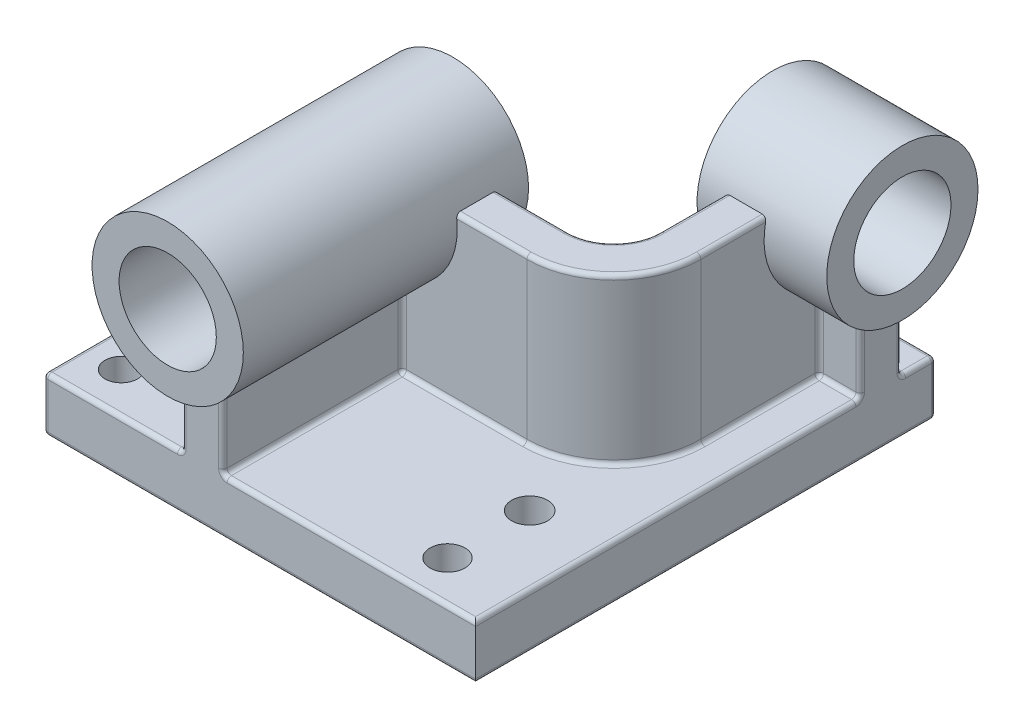
SolidWorks part; units mm, degrees
material "AISI 1020"
ref_plane "Front Plane" through (0, 0, 0) normal (0, 0, 1) x (1, 0, 0)
ref_plane "Top Plane" through (0, 0, 0) normal (0, 1, 0) x (1, 0, 0)
ref_plane "Right Plane" through (0, 0, 0) normal (1, 0, 0) x (0, 0, -1)
sketch "Sketch1" plane through (0, 0, 0) normal (0, 1, 0) x (1, 0, 0)
  line L0 (-200, 0) -> (0, 0)
  line L5 (0, 0) -> (0, 213)
  line L7 (-200, 0) -> (-200, 102)
  line L8 (-200, 102) -> (-59.2598, 102)
  line L9 (-38, 123.2598) -> (-38, 213)
  line L11 (-38, 213) -> (0, 213)
  arc A0 (-59.2598, 102) -> (-38, 123.2598) centre (-59.2598, 123.2598) ccw
  dimension "D1" = 200
  dimension "D2" = 213
  dimension "D3" = 38
  dimension "D4" = 102
extrude "Boss-Extrude1" add sketch "Sketch1" along normal blind 25
sketch "Sketch2" plane through (0, 25, 0) normal (0, 1, 0) x (1, 0, 0)
  line L0 (-200, 0) -> (0, 0) construction
  line L1 (-117, 0) -> (-136, 0)
  line L2 (-117, 0) -> (-117, 102)
  line L3 (-117, 102) -> (-136, 102)
  line L4 (-136, 0) -> (-136, 102)
  line L5 (-59.2598, 102) -> (-200, 102) construction
  line L6 (-200, 102) -> (-200, 0) construction
  dimension "D1" = 83
  dimension "D2" = 19
extrude "Boss-Extrude2" add sketch "Sketch2" along normal blind 76
sketch "Sketch3" plane through (0, 25, 0) normal (0, 1, 0) x (1, 0, 0)
  line L0 (-117, 102) -> (-59.2598, 102)
  line L1 (-38, 123.2598) -> (-38, 213)
  arc A0 (-59.2598, 102) -> (-38, 123.2598) centre (-59.2598, 123.2598) ccw
  arc A1 (-59.2598, 102) -> (-38, 123.2598) centre (-59.2598, 123.2598) ccw construction
extrude "Extrude-Thin1" add sketch "Sketch3" along normal blind 76 thin
sketch "Sketch4" plane through (0, 25, 0) normal (0, 1, 0) x (1, 0, 0)
  line L0 (0, 0) -> (0, 213) construction
  line L1 (0, 197) -> (-19, 197)
  line L2 (0, 197) -> (0, 178)
  line L3 (0, 178) -> (-19, 178)
  line L4 (-19, 197) -> (-19, 178)
  line L5 (-19, 123.2598) -> (-19, 213) construction
  line L6 (0, 213) -> (-19, 213) construction
  dimension "D1" = 35
  dimension "D2" = 19
extrude "Boss-Extrude3" add sketch "Sketch4" along normal blind 76
sketch "Sketch6" plane through (0, 0, 0) normal (0, 0, 1) x (1, 0, 0)
  line L0 (-126.5, 101) -> (-126.5, 73.6878) construction
  line L1 (-136, 101) -> (-117, 101) construction
  circle A0 centre (-126.5, 94.9895) radius 35
  circle A1 centre (-126.5, 94.9895) radius 22.5
  dimension "D1" = 70
  dimension "D2" = 45
extrude "Boss-Extrude4" add sketch "Sketch6" against normal blind 116 and the other way blind 16 from offset 0
sketch "Sketch7" plane through (0, 0, 0) normal (0, 0, 1) x (1, 0, 0)
  circle A0 centre (-126.5, 94.9895) radius 22.5
extrude "Cut-Extrude1" cut sketch "Sketch7" against normal blind 116
sketch "Sketch8" plane through (0, 0, 0) normal (1, 0, 0) x (0, 0, -1)
  line L0 (187.5, 101) -> (187.5, 71.9374) construction
  line L1 (178, 101) -> (197, 101) construction
  circle A0 centre (187.5, 92.0529) radius 35
  circle A1 centre (187.5, 92.0529) radius 22.5
  dimension "D1" = 70
  dimension "D2" = 45
extrude "Boss-Extrude5" add sketch "Sketch8" against normal blind 50 and the other way blind 10 from offset 0
sketch "Sketch9" plane through (0, 0, 0) normal (1, 0, 0) x (0, 0, -1)
  circle A0 centre (187.5, 92.0529) radius 22.5
extrude "Cut-Extrude2" cut sketch "Sketch9" against normal blind 50
sketch "Sketch10" plane through (0, 25, 0) normal (0, 1, 0) x (1, 0, 0)
  line L0 (-117, 0) -> (0, 0) construction
  line L1 (0, 0) -> (0, 178) construction
  circle A0 centre (-32, 19) radius 8.0817
  circle A1 centre (-32, 57) radius 8.2894
  dimension "D1" = 38
  dimension "D2" = 19
  dimension "D3" = 32
extrude "Cut-Extrude3" cut sketch "Sketch10" against normal blind 25
sketch "Sketch11" plane through (0, 25, 0) normal (0, 1, 0) x (1, 0, 0)
  line L0 (-200, 102) -> (-200, 0) construction
  line L1 (-200, 0) -> (-136, 0) construction
  circle A0 centre (-183, 19) radius 7.5179
  circle A1 centre (-183, 57) radius 7.8834
  dimension "D1" = 38
  dimension "D2" = 17
  dimension "D3" = 19
extrude "Cut-Extrude4" cut sketch "Sketch11" against normal blind 25
sketch "Sketch13" plane through (0, 0, 0) normal (1, 0, 0) x (0, 0, -1)
sketch_block_instance "Block1-1"
sketch_block "Block1"
fillet "Fillet2" radius 2 41 edges at (-200, 0, -51) (0, 41.6834, -178) (-19, 41.6834, -178) (-19, 41.6834, -197) (0, 41.6834, -197) (-38, 34.0395, -213) (-19, 46.5395, -213) (-200, 12.5, -102) (0, 25, -89) (0, 12.5, -213) (-200, 12.5, 0) (-9.5, 25, -213) (-58.5, 25, 0) (-168, 25, -102) (-117, 25, -41.5) (-136, 25, -51) (-75.6399, 101, -102) (-19, 25, -150.6299) (-38, 101, -138.4614) (-44.2269, 101, -108.2269) (-88.1299, 25, -83) (-30.7918, 25, -94.7918) (-19, 101, -138.4614) (-30.7918, 101, -94.7918) (-200, 25, -51) (-19, 25, -205) (0, 25, -205) (-9.5, 25, -197) (-9.5, 25, -178) (-75.6399, 101, -83) (-117, 43.1517, -83) (-129.6299, 0, -102) (-136, 43.1517, 0) (-44.2269, 0, -108.2269) (-136, 43.1517, -102) (-117, 43.1517, 0) (-38, 0, -168.1299) (-19, 0, -213) (-168, 25, 0) (0, 0, -106.5) (-100, 0, 0)
